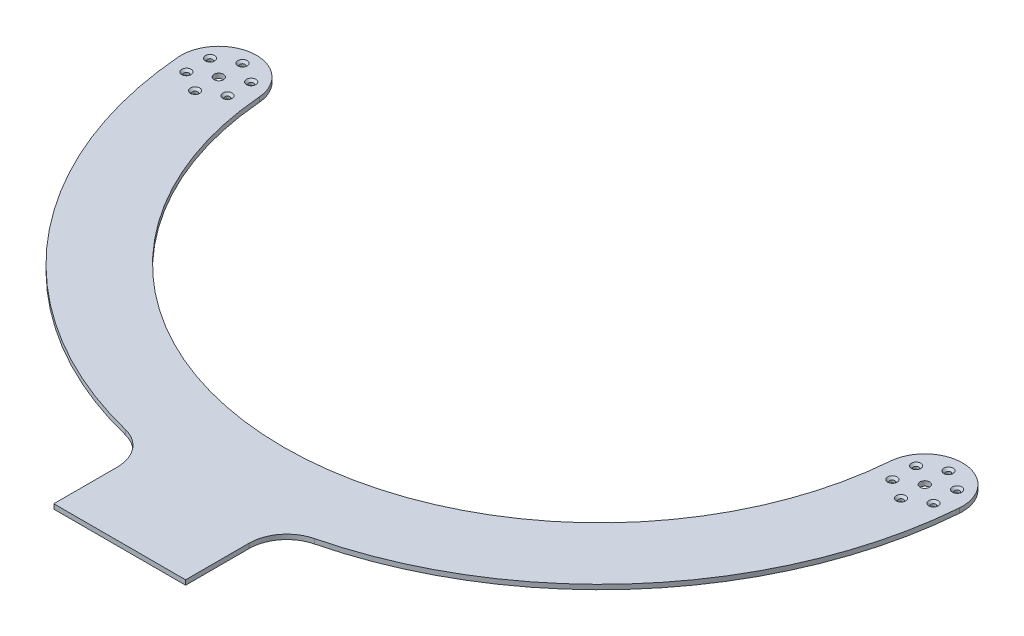
SolidWorks part; units mm, degrees
material "6061-T6 (SS)"
ref_plane "Front" through (0, 0, 0) normal (0, 0, 1) x (1, 0, 0)
ref_plane "Top" through (0, 0, 0) normal (0, 1, 0) x (1, 0, 0)
ref_plane "Right" through (0, 0, 0) normal (1, 0, 0) x (0, 0, -1)
sketch "Sketch1" plane through (0, 0, 0) normal (0, 1, 0) x (1, 0, 0)
  line L0 (44.45, 0) -> (-44.45, 0)
  line L1 (-44.45, 0) -> (-44.45, 63.5)
  line L2 (44.45, 0) -> (44.45, 63.5)
  circle A0 centre (0, 324.021) radius 206.375 construction
  circle A1 centre (-238.125, 304.971) radius 50.8 construction
  circle A2 centre (238.125, 304.971) radius 50.8 construction
  arc A3 (-212.8059, 306.9965) -> (-263.4441, 302.9454) centre (-238.125, 304.971) ccw
  arc A4 (-212.8059, 306.9965) -> (212.8059, 306.9965) centre (0, 324.021) ccw
  arc A5 (-263.4441, 302.9454) -> (-44.45, 63.5) centre (0, 324.021) ccw
  arc A6 (263.4441, 302.9454) -> (212.8059, 306.9965) centre (238.125, 304.971) ccw
  arc A7 (44.45, 63.5) -> (263.4441, 302.9454) centre (0, 324.021) ccw
  point P4 (0, 0)
  dimension "D1" = 412.75
  dimension "D2" = 101.6
  dimension "D3" = 19.05
  dimension "D4" = 25.4
  dimension "D5" = 19.05
  dimension "D6" = 63.5
  dimension "D7" = 88.9
extrude "Boss-Extrude1" add sketch "Sketch1" along normal blind 3.175
sketch "Sketch2" plane through (0, 3.175, 0) normal (0, 1, 0) x (1, 0, 0)
  circle A0 centre (-238.125, 304.971) radius 3.175
  circle A1 centre (238.125, 304.971) radius 3.175
  arc A2 (-212.8059, 306.9965) -> (-263.4441, 302.9454) centre (-238.125, 304.971) ccw construction
  arc A4 (263.4441, 302.9454) -> (212.8059, 306.9965) centre (238.125, 304.971) ccw construction
  dimension "D1" = 6.35
extrude "Cut-Extrude1" cut sketch "Sketch2" against normal through all
fillet "Fillet1" radius 25.4 2 edges at (44.45, 1.5875, -63.5) (-44.45, 1.5875, -63.5)
sketch "Sketch6" plane through (0, 3.175, 0) normal (0, 1, 0) x (1, 0, 0)
  line L0 (0, -50) -> (0, 50) construction
  circle A0 centre (238.125, 304.971) radius 16 construction
  circle A1 centre (-238.125, 304.971) radius 16 construction
  point P5 (238.125, 320.971)
  point P13 (251.9814, 312.971)
  point P14 (251.9814, 296.971)
  point P15 (238.125, 288.971)
  point P16 (224.2686, 296.971)
  point P17 (224.2686, 312.971)
  point P22 (-224.2686, 312.971)
  point P23 (-224.2686, 296.971)
  point P24 (-238.125, 288.971)
  point P25 (-251.9814, 296.971)
  point P26 (-251.9814, 312.971)
  point P27 (-238.125, 320.971)
  dimension "D2" = 32
  dimension "D1" = 6
hole_wizard "CSK for M3 Flat Head Machine Screw1" positions "Sketch6" profile "Sketch7" countersink size "M3" standard "ANSI Metric" end condition up to next
sketch "Sketch7" plane through (-238.125, 3.175, -320.971) normal (1, 0, 0) x (0, 0, 1)
  line L0 (0, 0) -> (0, 3.175)
  line L1 (0, 3.175) -> (1.7, 3.175)
  line L2 (1.7, 3.175) -> (1.7, 1.45)
  line L3 (1.7, 1.45) -> (3.15, 0)
  line L5 (3.15, 0) -> (0, 0)
  line L6 (-1.7, 1.45) -> (-3.15, 0) construction
  line L11 (0, -6.35) -> (0, 107.95) construction
  dimension "Thru Hole Dia." = 3.4
  dimension "Thru Hole Depth" = 3.175
  dimension "Near C'Sink Dia." = 6.3
  dimension "Near C'Sink Angle" = 90
